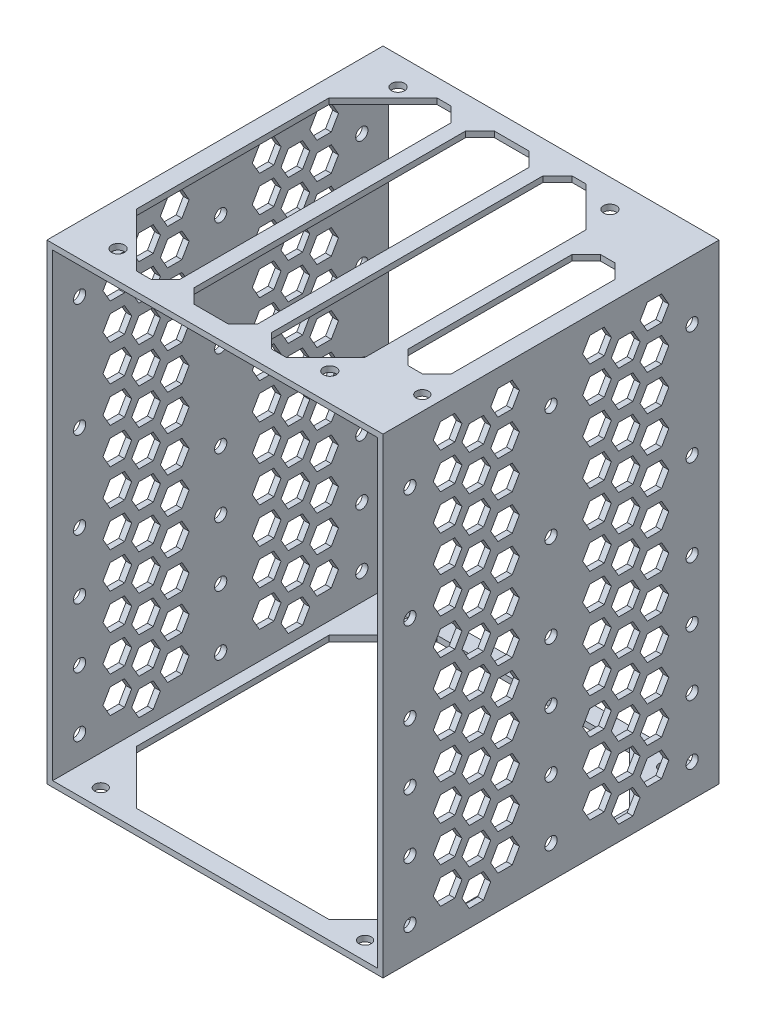
SolidWorks part; units mm, degrees
ref_plane "Front Plane" through (0, 0, 0) normal (0, 0, 1) x (1, 0, 0)
ref_plane "Top Plane" through (0, 0, 0) normal (0, 1, 0) x (1, 0, 0)
ref_plane "Right Plane" through (0, 0, 0) normal (1, 0, 0) x (0, 0, -1)
sketch "Sketch1" plane through (0, 0, 0) normal (0, 0, 1) x (1, 0, 0)
  line L0 (-45.2, 26.84) -> (45.2, 26.84)
  line L1 (45.2, 26.84) -> (45.2, -101.16)
  line L2 (45.2, -101.16) -> (-45.2, -101.16)
  line L3 (-45.2, -101.16) -> (-45.2, 26.84)
  line L5 (-46.8, 28.44) -> (46.8, 28.44)
  line L6 (-46.8, 28.44) -> (-46.8, -102.76)
  line L7 (-46.8, -102.76) -> (46.8, -102.76)
  line L8 (46.8, 28.44) -> (46.8, -102.76)
  dimension "D1" = 90.4
  dimension "D2" = 128
  dimension "D3" = 1.6
  dimension "D4" = 1.6
  dimension "D5" = 1.6
  dimension "D6" = 1.6
  dimension "D7" = 45.2
  dimension "D8" = 45.2
extrude "Boss-Extrude1" add sketch "Sketch1" along normal blind 93.6
sketch "Sketch2" plane through (46.8, 0, 0) normal (1, 0, 0) x (0, 0, -1)
  line L0 (-93.6, 28.44) -> (-93.6, -102.76)
  line L1 (-93.6, 28.44) -> (0, 28.44) construction
  line L2 (-93.6, -102.76) -> (-93.6, 28.44) construction
  line L3 (-93.6, -102.76) -> (0, -102.76) construction
  line L4 (-93.6, -85.36) -> (0, -85.36) construction
  line L5 (0, -102.76) -> (0, 28.44) construction
  line L6 (-93.6, -68.76) -> (0, -68.76) construction
  line L7 (-93.6, -52.16) -> (0, -52.16) construction
  line L8 (-93.6, -35.56) -> (0, -35.56) construction
  line L9 (-93.6, -3.96) -> (0, -3.96) construction
  line L10 (-93.6, -43.86) -> (0, -43.86)
  line L11 (-93.6, -60.46) -> (0, -60.46)
  line L12 (-93.6, -77.06) -> (0, -77.06)
  line L13 (-93.6, -93.66) -> (0, -93.66)
  line L14 (-93.6, -19.76) -> (0, -19.76)
  line L15 (-93.6, 11.84) -> (0, 11.84)
  line L16 (-93.6, -12.26) -> (0, -12.26)
  line L17 (-93.6, -84.56) -> (0, -84.56)
  line L18 (0, -84.56) -> (0, -86.16)
  line L19 (0, -86.16) -> (-93.6, -86.16)
  line L20 (-93.6, -67.96) -> (0, -67.96)
  line L21 (0, -67.96) -> (0, -69.56)
  line L22 (0, -69.56) -> (-93.6, -69.56)
  line L23 (-93.6, -51.36) -> (0, -51.36)
  line L24 (0, -51.36) -> (0, -52.96)
  line L25 (0, -52.96) -> (-93.6, -52.96)
  line L26 (-93.6, -34.76) -> (0, -34.76)
  line L27 (-93.6, -36.36) -> (0, -36.36)
  line L29 (-93.6, -3.16) -> (0, -3.16)
  line L30 (0, -3.16) -> (0, -4.76)
  line L31 (0, -4.76) -> (-93.6, -4.76)
  circle A11 centre (-86.1, 11.84) radius 0.75
  circle A13 centre (-86.1, -19.76) radius 0.75
  circle A14 centre (-86.1, -43.86) radius 0.75
  circle A15 centre (-86.1, -60.46) radius 0.75
  circle A16 centre (-86.1, -77.06) radius 0.75
  circle A17 centre (-86.1, -93.66) radius 0.75
  circle A18 centre (-7.5, 11.84) radius 0.75
  circle A20 centre (-7.5, -19.76) radius 0.75
  circle A21 centre (-7.5, -43.86) radius 0.75
  circle A22 centre (-7.5, -60.46) radius 0.75
  circle A23 centre (-7.5, -77.06) radius 0.75
  circle A24 centre (-7.5, -93.66) radius 0.75
  circle A27 centre (-46.8, 11.84) radius 0.75
  circle A29 centre (-46.8, -19.76) radius 0.75
  circle A30 centre (-46.8, -43.86) radius 0.75
  circle A31 centre (-46.8, -60.46) radius 0.75
  circle A32 centre (-46.8, -77.06) radius 0.75
  circle A33 centre (-46.8, -93.66) radius 0.75
  point P48 (0, 0)
  point P96 (0, 0)
  dimension "D7" = 16.6
  dimension "D8" = 15.8
  dimension "D9" = 8.3
  dimension "D10" = 8.3
  dimension "D11" = 8.3
  dimension "D12" = 8.3
  dimension "D13" = 1.5
  dimension "D14" = 7.5
  dimension "D15" = 7.5
  dimension "D16" = 1.5
  dimension "D17" = 1.5
  dimension "D18" = 1.5
  dimension "D19" = 1.5
  dimension "D20" = 1.5
  dimension "D21" = 1.5
  dimension "D22" = 1.5
  dimension "D23" = 1.5
  dimension "D24" = 1.5
  dimension "D25" = 1.5
  dimension "D26" = 1.5
  dimension "D39" = 1.5
  dimension "D1" = 17.4
  dimension "D2" = 16.6
  dimension "D3" = 16.6
  dimension "D4" = 16.6
  dimension "D5" = 31.6
  dimension "D6" = 32.4
  dimension "D27" = 8.3
  dimension "D28" = 0.8
  dimension "D29" = 0.8
  dimension "D30" = 0.8
  dimension "D31" = 0.8
  dimension "D32" = 0.8
  dimension "D33" = 0.8
  dimension "D34" = 0.8
  dimension "D35" = 0.8
  dimension "D36" = 0.8
  dimension "D37" = 0.8
  dimension "D38" = 15
extrude "Cut-Extrude1" cut sketch "Sketch2" against normal blind 100 contours L15 A11 | L15 A11 | L15 A18 | L15 A18 | L14 A13 | L14 A13 | L10 A21 | L10 A14 | L11 A15 | L11 A22 | L11 A22 | L12 A16 | L12 A16 | L12 A23 | L13 A17 | L13 A17 | L12 A23 | L13 A24 | L13 A24 | A20 | A21 | A14 | A15 | A27 | A29 | A30 | A31 | A32 | A33 region at (46.8, -19.4417, 86.1) region at (46.8, -20.0783, 86.1) region at (46.8, -44.1783, 7.5) region at (46.8, -43.5417, 86.1) region at (46.8, -60.1417, 7.5) region at (46.8, -60.7783, 7.5) region at (46.8, -60.1417, 86.1) region at (46.8, -76.7417, 7.5) region at (46.8, -77.3783, 7.5) region at (46.8, -76.7417, 86.1) region at (46.8, -77.3783, 86.1) region at (46.8, -93.3417, 7.5) region at (46.8, -93.9783, 7.5) region at (46.8, -93.3417, 86.1) region at (46.8, -93.9783, 86.1) region at (46.8, 12.1583, 7.5) region at (46.8, 11.5217, 7.5) region at (46.8, 12.1583, 86.1) region at (46.8, 11.5217, 86.1)
sketch "Sketch6" plane through (46.8, 0, 0) normal (1, 0, 0) x (0, 0, -1)
  line L18 (-93.6, 28.44) -> (0, 28.44) construction
  line L26 (-79.6, 19.9759) -> (-77.6, 23.44)
  line L27 (-77.6, 23.44) -> (-73.6, 23.44)
  line L28 (-73.6, 23.44) -> (-71.6, 19.9759)
  line L29 (-71.6, 19.9759) -> (-73.6, 16.5118)
  line L30 (-73.6, 16.5118) -> (-77.6, 16.5118)
  line L31 (-77.6, 16.5118) -> (-79.6, 19.9759)
  line L32 (-71.6, 15.4759) -> (-69.6, 18.94)
  line L33 (-69.6, 18.94) -> (-65.6, 18.94)
  line L34 (-65.6, 18.94) -> (-63.6, 15.4759)
  line L35 (-63.6, 15.4759) -> (-65.6, 12.0118)
  line L36 (-65.6, 12.0118) -> (-69.6, 12.0118)
  line L37 (-69.6, 12.0118) -> (-71.6, 15.4759)
  line L38 (-63.6, 19.9759) -> (-61.6, 23.44)
  line L39 (-61.6, 23.44) -> (-57.6, 23.44)
  line L40 (-57.6, 23.44) -> (-55.6, 19.9759)
  line L41 (-55.6, 19.9759) -> (-57.6, 16.5118)
  line L42 (-57.6, 16.5118) -> (-61.6, 16.5118)
  line L43 (-61.6, 16.5118) -> (-63.6, 19.9759)
  line L44 (-38, 19.9759) -> (-36, 23.44)
  line L45 (-36, 23.44) -> (-32, 23.44)
  line L46 (-32, 23.44) -> (-30, 19.9759)
  line L47 (-30, 19.9759) -> (-32, 16.5118)
  line L48 (-32, 16.5118) -> (-36, 16.5118)
  line L49 (-36, 16.5118) -> (-38, 19.9759)
  line L50 (-30, 14.9759) -> (-28, 18.44)
  line L51 (-28, 18.44) -> (-24, 18.44)
  line L52 (-24, 18.44) -> (-22, 14.9759)
  line L53 (-22, 14.9759) -> (-24, 11.5118)
  line L54 (-24, 11.5118) -> (-28, 11.5118)
  line L55 (-28, 11.5118) -> (-30, 14.9759)
  line L56 (-22, 19.9759) -> (-20, 23.44)
  line L57 (-20, 23.44) -> (-16, 23.44)
  line L58 (-16, 23.44) -> (-14, 19.9759)
  line L59 (-14, 19.9759) -> (-16, 16.5118)
  line L60 (-16, 16.5118) -> (-20, 16.5118)
  line L61 (-20, 16.5118) -> (-22, 19.9759)
  circle A0 centre (-86.1, 11.84) radius 0.75 construction
  circle A1 centre (-7.5, 11.84) radius 0.75 construction
  dimension "D1" = 120
  dimension "D2" = 120
  dimension "D3" = 120
  dimension "D4" = 4
  dimension "D5" = 4
  dimension "D6" = 4
  dimension "D7" = 120
  dimension "D8" = 120
  dimension "D9" = 120
  dimension "D10" = 4
  dimension "D11" = 4
  dimension "D12" = 4
  dimension "D13" = 2.25
  dimension "D14" = 120
  dimension "D15" = 120
  dimension "D16" = 120
  dimension "D17" = 4
  dimension "D18" = 4
  dimension "D19" = 4
  dimension "D20" = 4
  dimension "D21" = 4
  dimension "D22" = 4
  dimension "D23" = 120
  dimension "D24" = 120
  dimension "D25" = 120
  dimension "D26" = 4
  dimension "D27" = 4
  dimension "D28" = 4
  dimension "D29" = 120
  dimension "D30" = 120
  dimension "D31" = 6.5
  dimension "D32" = 4
  dimension "D33" = 5
  dimension "D34" = 5
  dimension "D35" = 4
  dimension "D36" = 4
  dimension "D37" = 5
  dimension "D38" = 10
  dimension "D39" = 5
  dimension "D40" = 4
  dimension "D41" = 4
  dimension "D42" = 6.5
  dimension "D43" = 4
extrude "Cut-Extrude4" cut sketch "Sketch6" against normal blind 100
hole_wizard "M3 Clearance Hole1" positions "Sketch7" profile "Sketch8" hole size "M3" standard "ANSI Metric" end condition through all
sketch "Sketch7" plane through (-46.8, 0, 0) normal (-1, 0, 0) x (0, 0, 1)
  point P0 (7.5, 11.84)
  point P3 (86.1, 11.84)
  point P6 (7.5, -19.76)
  point P9 (7.5, -43.86)
  point P12 (86.1, -19.76)
  point P15 (86.1, -43.86)
  point P18 (86.1, -60.46)
  point P21 (86.1, -77.06)
  point P26 (7.5, -93.66)
  point P29 (7.5, -77.06)
  point P32 (7.5, -60.46)
  point P40 (86.1, -93.66)
  point P46 (46.8, -77.06)
  point P49 (46.8, -93.66)
  point P52 (46.8, -60.46)
  point P55 (46.8, -43.86)
  point P58 (46.8, -19.76)
  point P61 (46.8, 11.84)
  point P65 (0, 0)
sketch "Sketch8" plane through (-46.8, 11.84, 7.5) normal (0, 1, 0) x (0, 0, 1)
  line L0 (0, 0) -> (0, 93.6)
  line L1 (0, 93.6) -> (1.7, 93.6)
  line L2 (1.7, 93.6) -> (1.7, 0)
  line L5 (1.7, 0) -> (0, 0)
  line L11 (0, -6.35) -> (0, 107.95) construction
  dimension "Thru Hole Dia." = 3.4
  dimension "Thru Hole Depth" = 93.6
sketch "Sketch9" plane through (0, 0, 0) normal (0, 0, 1) x (1, 0, 0)
  line L1 (-30, -108.3026) -> (30, -108.3026)
  line L2 (-30, -108.3026) -> (-30, -39.5314)
  line L3 (-30, -39.5314) -> (30, -39.5314)
  line L4 (30, -108.3026) -> (30, -39.5314)
  dimension "D1" = 30
  dimension "D2" = 30
sketch "Sketch10" plane through (0, -102.76, 0) normal (0, -1, 0) x (1, 0, 0)
  line L0 (45.2, 93.6) -> (-45.2, 93.6) construction
  line L3 (-46.8, 0) -> (46.8, 0) construction
  line L5 (-46.8, 0) -> (46.8, 0) construction
  line L6 (-46.8, 93.6) -> (46.8, 93.6) construction
  line L7 (-46.8, 93.6) -> (-46.8, 0) construction
  line L8 (46.8, 93.6) -> (46.8, 0) construction
  circle A0 centre (-36.8, 88.6) radius 2.9453
  circle A1 centre (-36.8, 5) radius 1.9301
  circle A2 centre (36.8, 5) radius 1.9498
  circle A3 centre (36.8, 88.6) radius 2.427
  dimension "D1" = 5
  dimension "D2" = 10
  dimension "D3" = 10
  dimension "D4" = 5
  dimension "D5" = 10
  dimension "D6" = 5
  dimension "D7" = 5
  dimension "D8" = 10
hole_wizard "M3 Clearance Hole2" positions "Sketch11" profile "Sketch12" hole size "M3" standard "ANSI Metric" end condition up to next
sketch "Sketch11" plane through (0, -102.76, 0) normal (0, -1, 0) x (-1, 0, 0)
  point P0 (-36.8, -5)
  point P3 (-36.8, -88.6)
  point P6 (36.8, -88.6)
  point P9 (36.8, -5)
sketch "Sketch12" plane through (36.8, -102.76, 5) normal (1, 0, 0) x (0, 0, -1)
  line L0 (0, 0) -> (0, 1.6)
  line L1 (0, 1.6) -> (1.7, 1.6)
  line L2 (1.7, 1.6) -> (1.7, 0)
  line L5 (1.7, 0) -> (0, 0)
  line L11 (0, -6.35) -> (0, 107.95) construction
  dimension "Thru Hole Dia." = 3.4
  dimension "Thru Hole Depth" = 1.6
pattern_linear "LPattern1" count 12 spacing 10 along (0, -1, 0) of "Cut-Extrude4"
sketch "Sketch16" plane through (0, 28.44, 0) normal (0, 1, 0) x (1, 0, 0)
  line L0 (46.8, -93.6) -> (46.8, 0) construction
  line L1 (46.8, -93.6) -> (-46.8, -93.6) construction
  circle A0 centre (42.75, -78.6) radius 1.7
  dimension "D1" = 3.4
  dimension "D2" = 4.05
  dimension "D3" = 15
extrude "Cut-Extrude6" cut sketch "Sketch16" against normal blind 141
hole_wizard "M3 Clearance Hole3" positions "Sketch17" profile "Sketch18" hole size "M3" standard "ANSI Metric" end condition up to next
sketch "Sketch17" plane through (0, 28.44, 0) normal (0, 1, 0) x (1, 0, 0)
  line L0 (-46.8, -93.6) -> (-46.8, 0) construction
  line L2 (46.8, 0) -> (-46.8, 0) construction
  circle A0 centre (42.75, -78.6) radius 1.7 construction
  point P0 (-34.8, -7.8)
  point P2 (-34.8, -85.8)
  point P4 (24.2, -85.8)
  point P6 (24.2, -7.8)
  dimension "D1" = 12
  dimension "D2" = 7.8
  dimension "D3" = 59
  dimension "D4" = 78
  dimension "D5" = 18.55
sketch "Sketch18" plane through (-34.8, 28.44, 7.8) normal (1, 0, 0) x (0, 0, 1)
  line L0 (0, 0) -> (0, 1.6)
  line L1 (0, 1.6) -> (1.8, 1.6)
  line L2 (1.8, 1.6) -> (1.8, 0)
  line L5 (1.8, 0) -> (0, 0)
  line L11 (0, -6.35) -> (0, 107.95) construction
  dimension "Thru Hole Dia." = 3.6
  dimension "Thru Hole Depth" = 1.6
sketch "Sketch19" plane through (0, 28.44, 0) normal (0, 1, 0) x (1, 0, 0)
  line L15 (-26.8, -5) -> (-41.8, -20)
  line L16 (-41.8, -73.6) -> (-26.8, -88.6)
  line L17 (41.8, -73.6) -> (29.8, -73.6)
  line L18 (29.8, -73.6) -> (14.8, -88.6)
  line L19 (41.8, -88.6) -> (41.8, -5)
  line L20 (-41.8, -88.6) -> (41.8, -88.6)
  line L21 (-41.8, -5) -> (-41.8, -88.6)
  line L22 (41.8, -5) -> (-41.8, -5)
  line L23 (41.8, -88.6) -> (41.8, -5)
  line L24 (-26.8, -88.6) -> (41.8, -88.6)
  line L25 (-41.8, -20) -> (-41.8, -73.6)
  line L26 (41.8, -5) -> (-26.8, -5)
  line L27 (41.8, -20) -> (29.8, -20)
  line L28 (29.8, -20) -> (14.8, -5)
  line L29 (-18.8, -5) -> (-18.8, -88.6)
  line L30 (-14.8, -88.6) -> (-14.8, -5)
  line L31 (6.8, -5) -> (6.8, -88.6)
  line L32 (2.8, -5) -> (2.8, -88.6)
  line L33 (29.8, -73.6) -> (29.8, -20)
  line L34 (25.8, -77.6) -> (25.8, -16)
  dimension "D1" = 5
  dimension "D2" = 12
  dimension "D3" = 4
  dimension "D6" = 4
  dimension "D7" = 8
  dimension "D8" = 8
  dimension "D9" = 4
extrude "Cut-Extrude7" cut sketch "Sketch19" against normal blind 1.6 contours L29 L26 L15 L25 L16 L24 | L32 L26 L30 L24 | L18 L34 L28 L26 L31 L24 | L33 L17 L23 L27 region at (-29.4386, 28.44, 46.8) region at (-6, 28.44, 46.8) region at (15.819, 28.44, 46.8) region at (35.8, 28.44, 46.8)
chamfer "Chamfer1" distance 4 angle 45 12 edges at (-18.8, 27.64, 88.6) (2.8, 27.64, 88.6) (-14.8, 27.64, 88.6) (6.8, 27.64, 88.6) (6.8, 27.64, 5) (-14.8, 27.64, 5) (-18.8, 27.64, 5) (2.8, 27.64, 5) (41.8, 27.64, 73.6) (41.8, 27.64, 20) (29.8, 27.64, 20) (29.8, 27.64, 73.6)
sketch "Sketch20" plane through (0, -102.76, 0) normal (0, -1, 0) x (1, 0, 0)
  line L10 (-41.8, 20) -> (-26.8, 5)
  line L11 (26.8, 5) -> (41.8, 20)
  line L12 (41.8, 73.6) -> (26.8, 88.6)
  line L13 (-26.8, 88.6) -> (-41.8, 73.6)
  line L14 (41.8, 5) -> (41.8, 88.6)
  line L15 (-41.8, 5) -> (41.8, 5)
  line L16 (-41.8, 88.6) -> (-41.8, 5)
  line L17 (41.8, 88.6) -> (-41.8, 88.6)
  line L18 (41.8, 20) -> (41.8, 73.6)
  line L19 (-26.8, 5) -> (26.8, 5)
  line L20 (-41.8, 73.6) -> (-41.8, 20)
  line L21 (26.8, 88.6) -> (-26.8, 88.6)
  dimension "D1" = 5
extrude "Cut-Extrude8" cut sketch "Sketch20" against normal blind 10
